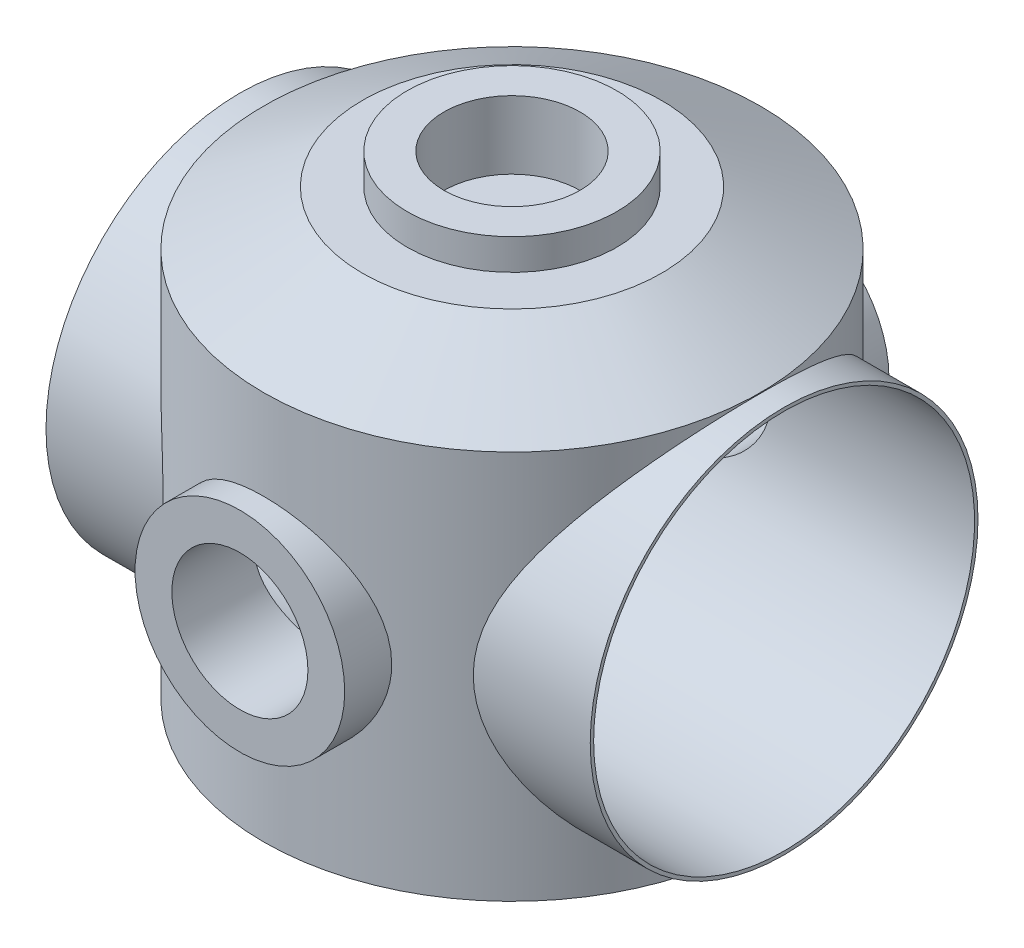
SolidWorks part; units mm, degrees
ref_plane "Front Plane" through (0, 0, 0) normal (0, 0, 1) x (1, 0, 0)
ref_plane "Top Plane" through (0, 0, 0) normal (0, 1, 0) x (1, 0, 0)
ref_plane "Right Plane" through (0, 0, 0) normal (1, 0, 0) x (0, 0, -1)
sketch "Sketch1" plane through (0, 0, 0) normal (0, 1, 0) x (1, 0, 0)
  line L1 (-12.9047, 12.9047) -> (12.9047, 12.9047)
  line L2 (-12.9047, 12.9047) -> (-12.9047, -12.9047)
  line L3 (-12.9047, -12.9047) -> (12.9047, -12.9047)
  line L4 (12.9047, 12.9047) -> (12.9047, -12.9047)
  line L5 (-12.9047, 12.9047) -> (12.9047, -12.9047) construction
  line L6 (-12.9047, -12.9047) -> (12.9047, 12.9047) construction
  circle A0 centre (0, 0) radius 18.25
  dimension "D1" = 36.5
extrude "Boss-Extrude1" add sketch "Sketch1" along normal blind 28.6 contours L4 L1 L2 L3 region at (0, 0, 0)
ref_plane "Plane1" through (0, 0, 0) normal (-1, 0, 0) x (0, 0, 1)
ref_plane "Plane3" through (0, 14.3, 0) normal (0, -1, 0) x (-1, 0, 0)
sketch "Sketch2" plane through (0, 0, 0) normal (-1, 0, 0) x (0, 0, 1)
  line L3 (0, 0) -> (0, -3.98)
  line L4 (0, -3.98) -> (11, -3.98)
  line L5 (11, -3.98) -> (18.25, 0)
  line L6 (18.25, 0) -> (0, 0)
  dimension "D1" = 18.25
  dimension "D2" = 3.98
  dimension "D3" = 11
revolve "Revolve1" add sketch "Sketch2" angle 360 about L3
mirror "Mirror2" about plane through (0, 14.3, 0) normal (0, -1, 0) of "Revolve1"
extrude "Boss-Extrude3" add sketch "Sketch1<4>" along normal blind 28.6 contours L2 A0 | L1 A0 | L4 A0 | L3 A0 region at (0, 0, -15.0722) region at (-15.0722, 0, 0) region at (15.0722, 0, 0) region at (0, 0, 15.0722)
sketch "Sketch1<4>" plane through (0, 0, 0) normal (0, 1, 0) x (1, 0, 0) same geometry as "Sketch1"
sketch "Sketch4" plane through (0, 0, 0) normal (-1, 0, 0) x (0, 0, 1)
  line L0 (-55, 14.3) -> (55, 14.3) construction
  circle A0 centre (0, 14.3) radius 14.25
  point P4 (0, 0)
  dimension "D1" = 28.5
extrude "Cut-Extrude4" cut sketch "Sketch4" against normal through all both and the other way through all
sketch "Sketch5" plane through (0, 0, 0) normal (-1, 0, 0) x (0, 0, 1)
  circle A0 centre (0, 14.3) radius 14.25
  circle A1 centre (0, 14.3) radius 14
  dimension "D1" = 28.5
  dimension "D2" = 28
extrude "Boss-Extrude4" add sketch "Sketch5" along normal mid plane 40
sketch "Sketch6" plane through (0, 32.58, 0) normal (0, 1, 0) x (1, 0, 0)
  circle A0 centre (0, 0) radius 7.705
  dimension "D1" = 15.41
extrude "Boss-Extrude5" add sketch "Sketch6" along normal blind 2.27
sketch "Sketch7" plane through (0, 34.85, 0) normal (0, 1, 0) x (1, 0, 0)
  circle A0 centre (0, 0) radius 5
  dimension "D1" = 10
extrude "Cut-Extrude5" cut sketch "Sketch7" against normal blind 5
sketch "Sketch8" plane through (0, 0, 0) normal (0, 0, 1) x (1, 0, 0)
  line L0 (-55, 14.3) -> (55, 14.3) construction
  circle A1 centre (0, 14.3) radius 7.705
  point P4 (0, 0)
  dimension "D1" = 15.41
extrude "Boss-Extrude7" add sketch "Sketch8" against normal up to surface (3.4562 mm away) from offset 20 up to face at (11.4047, 14.561, 14.2476)
sketch "Sketch12" plane through (0, 0, 20) normal (0, 0, 1) x (1, 0, 0)
  circle A0 centre (0, 14.3) radius 5
  dimension "D1" = 10
mirror "Mirror5" about plane through (0, 0, 0) normal (0, 0, 1) of "Boss-Extrude7"
extrude "Cut-Extrude8" cut sketch "Sketch12" against normal through all both and the other way through all contours A0
